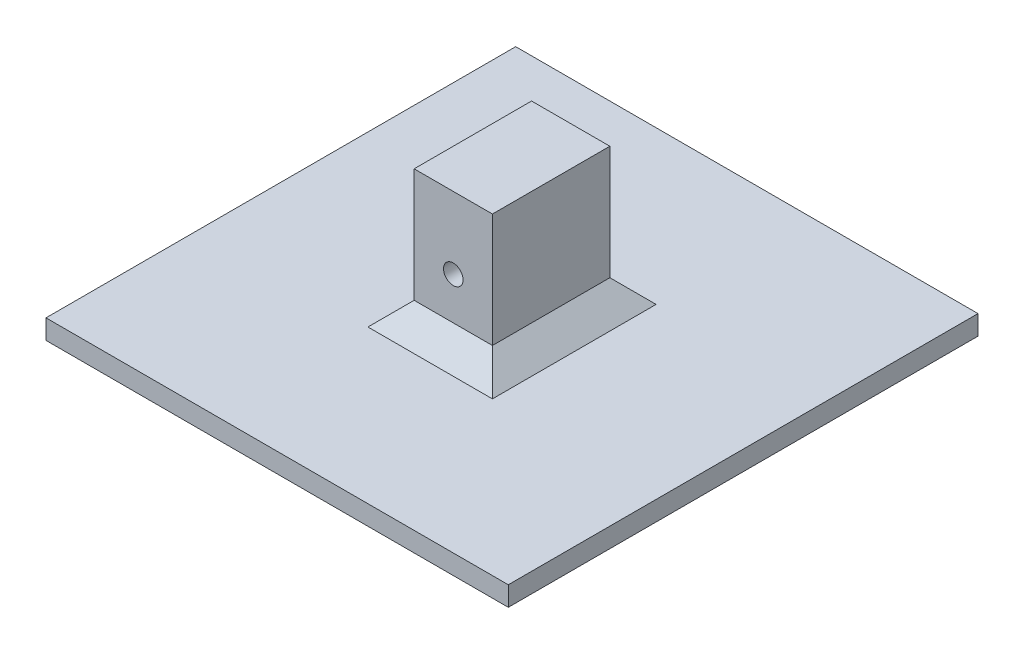
SolidWorks part; units mm, degrees
ref_plane "Front Plane" through (0, 0, 0) normal (0, 0, 1) x (1, 0, 0)
ref_plane "Top Plane" through (0, 0, 0) normal (0, 1, 0) x (1, 0, 0)
ref_plane "Right Plane" through (0, 0, 0) normal (1, 0, 0) x (0, 0, -1)
sketch "Sketch-Profile" plane through (0, 0, 0) normal (1, 0, 0) x (0, 0, -1)
  line L0 (-76.2, 6.35) -> (-76.2, 0)
  line L5 (-76.2, 6.35) -> (-19.05, 6.35)
  line L6 (-76.2, 0) -> (76.2, 0)
  line L7 (76.2, 6.35) -> (76.2, 0)
  line L8 (-76.2, 6.35) -> (76.2, 0) construction
  line L9 (-76.2, 0) -> (76.2, 6.35) construction
  line L10 (-19.05, 50.8) -> (-19.05, 6.35)
  line L11 (-19.05, 50.8) -> (19.05, 50.8)
  line L13 (19.05, 50.8) -> (19.05, 6.35)
  line L14 (-19.05, 50.8) -> (19.05, 6.35) construction
  line L15 (-19.05, 6.35) -> (19.05, 50.8) construction
  line L16 (19.05, 6.35) -> (76.2, 6.35)
  point P1 (0, 3.175)
  point P2 (0, 28.575)
  dimension "D1" = 6.35
  dimension "D2" = 50.8
  dimension "D3" = 152.4
  dimension "D4" = 38.1
extrude "Boss-Extrude1" add sketch "Sketch-Profile" along normal blind 12.7 and the other way blind 12.7
sketch "Sketch-Hole Location" plane through (0, 0, 19.05) normal (0, 0, 1) x (1, 0, 0)
  line L0 (0, 0) -> (0, 50.8) construction
  line L1 (12.7, 0) -> (-12.7, 0) construction
  line L2 (12.7, 50.8) -> (-12.7, 50.8) construction
  line L3 (43.2175, 27.5181) -> (-43.2175, 27.5181) construction
  point P6 (0, 27.5181)
sketch "Sketch5" plane through (0, 0, 19.05) normal (0, 0, 1) x (1, 0, 0)
  point P0 (0, 27.5181)
hole_wizard "1/4 (0.25) Diameter Hole1" positions "Sketch5" profile "Sketch4" hole size "1/4" standard "ANSI Inch" end condition through all
sketch "Sketch4" plane through (0, 27.5181, 19.05) normal (1, 0, 0) x (0, -1, 0)
  line L0 (0, 0) -> (0, 95.25)
  line L1 (0, 95.25) -> (3.175, 95.25)
  line L2 (3.175, 95.25) -> (3.175, 0)
  line L5 (3.175, 0) -> (0, 0)
  line L11 (0, -6.35) -> (0, 107.95) construction
  dimension "Thru Hole Dia." = 6.35
  dimension "Thru Hole Depth" = 95.25
sketch "Sketch6" plane through (0, 0, 0) normal (1, 0, 0) x (0, 0, -1)
  line L0 (76.2, 0) -> (76.2, 6.35) construction
  line L1 (-76.2, 0) -> (76.2, 0) construction
  line L2 (-76.2, 6.35) -> (-76.2, 0) construction
  line L3 (76.2, 0) -> (76.2, 6.35)
  line L4 (-76.2, 0) -> (76.2, 0)
  line L5 (-76.2, 6.35) -> (-76.2, 0)
  line L6 (-76.2, 6.35) -> (76.2, 6.35)
extrude "Boss-Extrude2" add sketch "Sketch6" along normal blind 75 and the other way blind 75
chamfer "Chamfer1" distance 7.5 angle 45 4 edges at (0, 6.35, 19.05) (-12.7, 6.35, 0) (0, 6.35, -19.05) (12.7, 6.35, 0)
